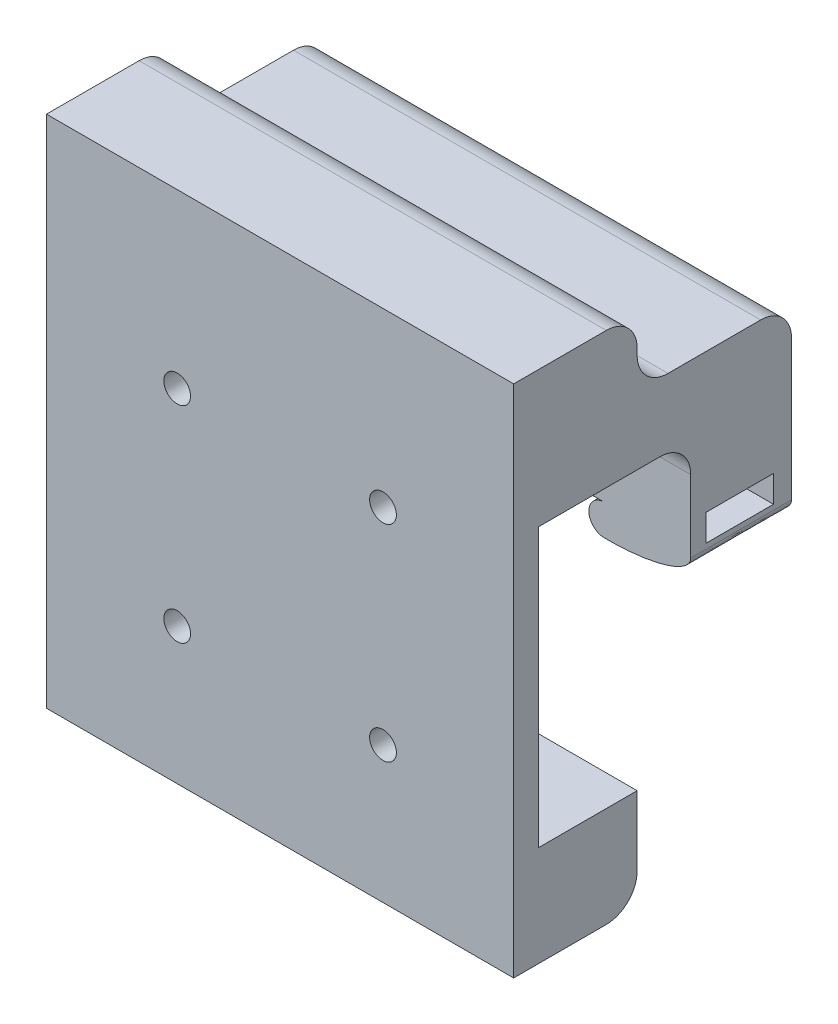
SolidWorks part; units mm, degrees
ref_plane "Front Plane" through (0, 0, 0) normal (0, 0, 1) x (1, 0, 0)
ref_plane "Top Plane" through (0, 0, 0) normal (0, 1, 0) x (1, 0, 0)
ref_plane "Right Plane" through (0, 0, 0) normal (1, 0, 0) x (0, 0, -1)
sketch "Sketch1" plane through (0, 0, 0) normal (0, 0, 1) x (1, 0, 0)
  line L1 (0, 0) -> (45.4, 0)
  line L2 (0, 0) -> (0, 50)
  line L3 (0, 50) -> (45.4, 50)
  line L4 (45.4, 0) -> (45.4, 50)
  dimension "D1" = 45.4
  dimension "D2" = 50
extrude "Boss-Extrude1" add sketch "Sketch1" along normal blind 12
sketch "Sketch2" plane through (0, 0, 0) normal (0, 0, -1) x (-1, 0, 0)
  line L0 (-45.4, 0) -> (-45.4, 50) construction
  line L1 (-45.4, 36.7633) -> (0, 36.7633)
  line L2 (-45.4, 36.7633) -> (-45.4, 9.7633)
  line L3 (-45.4, 9.7633) -> (0, 9.7633)
  line L4 (0, 36.7633) -> (0, 9.7633)
  line L5 (0, 50) -> (0, 0) construction
  dimension "D1" = 27
extrude "Cut-Extrude1" cut sketch "Sketch2" against normal blind 9.6
sketch "Sketch7" plane through (0, 0, 0) normal (0, 0, -1) x (-1, 0, 0)
  line L0 (-45.4, 36.7633) -> (-45.4, 50) construction
  line L1 (-45.4, 43.3816) -> (0, 43.3816)
  line L2 (-45.4, 43.3816) -> (-45.4, 36.7633)
  line L3 (-45.4, 36.7633) -> (0, 36.7633)
  line L4 (0, 43.3816) -> (0, 36.7633)
extrude "Boss-Extrude2" add sketch "Sketch7" along normal blind 15
sketch "Sketch8" plane through (0, 36.7633, 0) normal (0, -1, 0) x (1, 0, 0)
  line L0 (45.4, 9.6) -> (45.4, -15) construction
  line L1 (0, -15) -> (45.4, -15)
  line L2 (0, -15) -> (0, -5.2048)
  line L3 (0, -5.2048) -> (45.4, -5.2048)
  line L4 (45.4, -15) -> (45.4, -5.2048)
extrude "Boss-Extrude3" add sketch "Sketch8" along normal blind 12.52
sketch "Sketch10" plane through (0, 0, -15) normal (0, 0, -1) x (-1, 0, 0)
  line L0 (0, 27.2433) -> (-45.4, 27.2433) construction
  line L1 (0, 24.2433) -> (0, 43.3816) construction
  line L2 (-45.4, 43.3816) -> (-45.4, 24.2433) construction
  line L3 (0, 24.2433) -> (-45.4, 24.2433) construction
  line L5 (-37, 27.2433) -> (-8, 27.2433)
  line L7 (-37, 24.2433) -> (-8, 24.2433)
  arc A0 (-37, 27.2433) -> (-37, 24.2433) centre (-37, 25.7433) cw
  arc A1 (-8, 27.2433) -> (-8, 24.2433) centre (-8, 25.7433) ccw
  dimension "D1" = 3
extrude "Cut-Extrude2" cut sketch "Sketch10" against normal up to next
sketch "Sketch11" plane through (45.4, 0, 0) normal (1, 0, 0) x (0, 0, -1)
  line L1 (6.7048, 27.2433) -> (13.25, 27.2433)
  line L2 (6.7048, 27.2433) -> (6.7048, 29.8433)
  line L3 (6.7048, 29.8433) -> (13.25, 29.8433)
  line L4 (13.25, 27.2433) -> (13.25, 29.8433)
  line L5 (5.2048, 24.2433) -> (5.2048, 36.7633) construction
  line L6 (15, 43.3816) -> (15, 24.2433) construction
  line L7 (15, 24.2433) -> (5.2048, 24.2433) construction
  point P10 (0, 0)
  point P11 (13.25, 31.7479)
  point P12 (0, 0)
  point P13 (0, 0)
  dimension "D1" = 1.5
  dimension "D2" = 1.75
  dimension "D3" = 2.6
  dimension "D4" = 3
extrude "Cut-Extrude3" cut sketch "Sketch11" against normal through all
fillet "Fillet1" radius 2.5 2 edges at (0, 24.2433, -10.1024) (45.4, 24.2433, -10.1024) second distance 8 first distance on face at (0, 28.5433, -9.9774) first distance on face at (45.4, 28.5433, -9.9774)
fillet "Fillet2" radius 3 5 edges at (22.7, 0, 0) (22.7, 36.7633, -5.2048) (22.7, 50, 0) (22.7, 43.3816, 0) (22.7, 43.3816, -15)
sketch "Sketch13" plane through (0, 0, 12) normal (0, 0, 1) x (1, 0, 0)
  circle A0 centre (12.7, 33.2632) radius 1.3
  circle A1 centre (32.7, 33.2632) radius 1.3
  circle A2 centre (32.7, 13.2632) radius 1.3
  circle A3 centre (12.7, 13.2632) radius 1.3
  dimension "D1" = 2.6
extrude "Cut-Extrude4" cut sketch "Sketch13" against normal up to next
